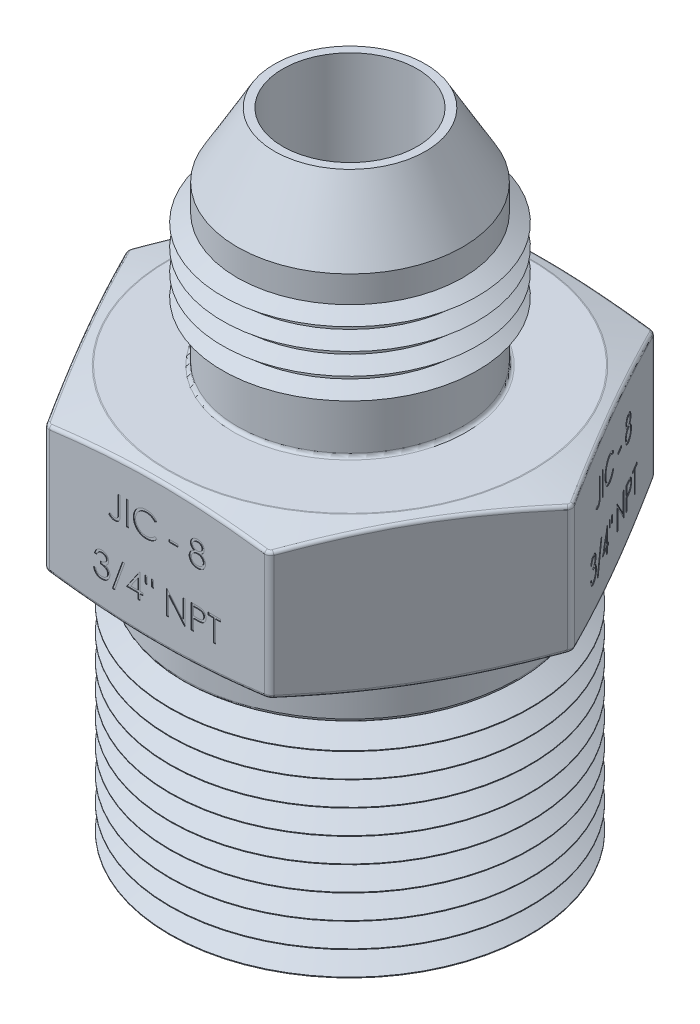
SolidWorks part; units mm, degrees
other "Fitting Body"
material "ASTM A36 Steel"
ref_plane "Front Plane" through (0, 0, 0) normal (0, 0, 1) x (1, 0, 0)
ref_plane "Top Plane" through (0, 0, 0) normal (0, 1, 0) x (1, 0, 0)
ref_plane "Right Plane" through (0, 0, 0) normal (1, 0, 0) x (0, 0, -1)
sketch "Sketch1" plane through (0, 0, 0) normal (0, 1, 0) x (1, 0, 0)
  line L1 (16.4978, 0) -> (8.2489, 14.2875)
  line L2 (8.2489, 14.2875) -> (-8.2489, 14.2875)
  line L3 (-8.2489, 14.2875) -> (-16.4978, 0)
  line L4 (-16.4978, 0) -> (-8.2489, -14.2875)
  line L5 (-8.2489, -14.2875) -> (8.2489, -14.2875)
  line L6 (8.2489, -14.2875) -> (16.4978, 0)
  circle A0 centre (0, 0) radius 14.2875 construction
  dimension "D1" = 28.575
extrude "Boss-Extrude1" add sketch "Sketch1" along normal mid plane 10.922
sketch "Sketch2" plane through (0, 5.461, 0) normal (0, 1, 0) x (1, 0, 0)
  circle A0 centre (0, 0) radius 13.462
  dimension "D1" = 26.924
extrude "Cut-Extrude1" cut sketch "Sketch2" against normal blind 8.255 draft 75 flip side to cut
sketch "Sketch3" plane through (0, -5.461, 0) normal (0, -1, 0) x (1, 0, 0)
  circle A0 centre (0, 0) radius 13.462 construction
  circle A1 centre (0, 0) radius 13.462
extrude "Cut-Extrude2" cut sketch "Sketch3" against normal blind 8.255 draft 75 flip side to cut
fillet "Fillet1" radius 0.508 6 edges at (8.2489, 0, 14.2875) (-8.2489, 0, 14.2875) (-16.4978, 0, 0) (-8.2489, 0, -14.2875) (8.2489, 0, -14.2875) (16.4978, 0, 0)
fillet "Fillet2" radius 0.254 25 edges at (16.4147, -4.6698, 0.0677) (8.266, -4.6698, -14.1817) (-8.1487, -4.6698, -14.2494) (-16.4147, -4.6698, -0.0677) (-8.266, -4.6698, 14.1817) (8.1487, -4.6698, 14.2494) (-8.1487, 4.6698, 14.2494) (-16.4147, 4.6698, 0.0677) (-8.266, 4.6698, -14.1817) (8.1487, 4.6698, -14.2494) (16.4147, 4.6698, -0.0677) (8.266, 4.6698, 14.1817) (0, 5.461, 13.462)
sketch "Sketch8" plane through (0, 5.461, 0) normal (0, 1, 0) x (1, 0, 0)
  circle A0 centre (0, 0) radius 8.3439
  dimension "D1" = 16.6878
extrude "Boss-Extrude6" add sketch "Sketch8" along normal blind 16.51
fillet "Fillet3" radius 0.254 1 edges at (0, 5.461, 8.3439)
sketch "Sketch Part Specs Info" plane through (0, 0, 14.2875) normal (0, 0, 1) x (1, 0, 0)
  line L0 (0, 0) -> (0, -3.1086) construction
  line L1 (0, 0) -> (0, 1.1201) construction
  line L2 (-7.9556, -3.1086) -> (7.9556, -3.1086) construction
  line L3 (-7.9556, 1.1201) -> (7.9556, 1.1201) construction
  line L4 (-7.9556, 4.4827) -> (-7.9556, -4.4827) construction
  text T0 "JIC - 8\r\n" font "Century Gothic" height 1.778
  text T1 "3/4\" NPT" font "Century Gothic" height 1.778
extrude "Cut Part Specs" cut sketch "Sketch Part Specs Info" against normal blind 0.0508
chamfer "Chamfer1" distance 4.7625 angle 30 1 edges at (0, 21.971, 8.3439) first distance on face at (0, 5.715, 8.3439)
sketch "Sketch12" plane through (0, 0, 0) normal (0, 0, 1) x (1, 0, 0)
  line L0 (0, 0) -> (0, 14.605) construction
  line L1 (0, 14.605) -> (0, 21.971) construction
  line L2 (5.5943, 21.971) -> (-5.5943, 21.971) construction
  line L3 (0, 14.605) -> (8.3439, 14.605) construction
  line L4 (8.3439, 5.715) -> (8.3439, 17.2085) construction
  line L5 (8.3439, 14.605) -> (9.4438, 14.605) construction
  line L6 (8.3439, 15.24) -> (8.3439, 13.97)
  line L7 (8.3439, 15.24) -> (9.4438, 14.605)
  line L8 (9.4438, 14.605) -> (8.3439, 13.97)
  dimension "D1" = 60
  dimension "D2" = 1.27
  dimension "D3" = 7.366
revolve "Revolve2" add sketch "Sketch12" angle 360 about L0
pattern_linear "LPattern2" count 4 spacing 1.5875 along (0, -1, 0) of "Revolve2"
sketch "Sketch4" plane through (0, -5.461, 0) normal (0, -1, 0) x (1, 0, 0)
  circle A0 centre (0, 0) radius 12.3825
  dimension "D1" = 24.765
extrude "Boss-Extrude7" add sketch "Sketch4" along normal blind 3.175
sketch "Sketch13" plane through (0, -8.636, 0) normal (0, -1, 0) x (1, 0, 0)
  circle A0 centre (0, 0) radius 13.335
  dimension "D1" = 26.67
extrude "Boss-Extrude8" add sketch "Sketch13" along normal offset from surface (16.637 mm away) 47.244 up to face at (0, 21.971, 5.5943)
sketch "Sketch14" plane through (0, 0, 0) normal (0, 0, 1) x (1, 0, 0)
  line L0 (0, 0) -> (0, -25.273) construction
  line L1 (-13.335, -25.273) -> (13.335, -25.273) construction
  line L2 (0, -25.273) -> (11.811, -25.273) construction
  line L3 (11.811, -25.273) -> (13.3822, -25.273) construction
  line L4 (13.3822, -25.273) -> (15.1965, -25.273) construction
  line L5 (15.1965, -24.3659) -> (15.1965, -26.1801)
  line L6 (13.3822, -24.3659) -> (13.3822, -26.1801) construction
  line L7 (15.1965, -24.3659) -> (13.3822, -24.3659)
  line L8 (13.3822, -24.3659) -> (11.811, -25.273)
  line L9 (11.811, -25.273) -> (13.3822, -26.1801)
  line L10 (13.3822, -26.1801) -> (15.1965, -26.1801)
  dimension "D1" = 60
  dimension "D2" = 1.8143
  dimension "D3" = 11.811
revolve "Cut-Revolve1" cut sketch "Sketch14" angle 360 about L0
pattern_linear "LPattern3" count 10 spacing 1.8143 along (0, 1, 0) of "Cut-Revolve1"
sketch "Sketch15" plane through (0, -25.273, 0) normal (0, -1, 0) x (1, 0, 0)
  circle A0 centre (0, 0) radius 4.9784
  dimension "D1" = 9.9568
extrude "Cut-Extrude3" cut sketch "Sketch15" against normal up to surface (47.244 mm away) up to face at (0, 21.971, 5.5943)
fillet "Fillet4" radius 0.254 3 edges at (0, -8.6145, 12.3825) (0, -5.461, 12.3825) (0, -5.461, -13.462)
pattern_circular "CirPattern1" count 3 over 360 about axis through (0, 36.052, 0) along (0, -1, 0) of "Cut Part Specs"
chamfer "Chamfer2" distance 0.508 angle 45 1 edges at (0, -25.273, -4.9784)
